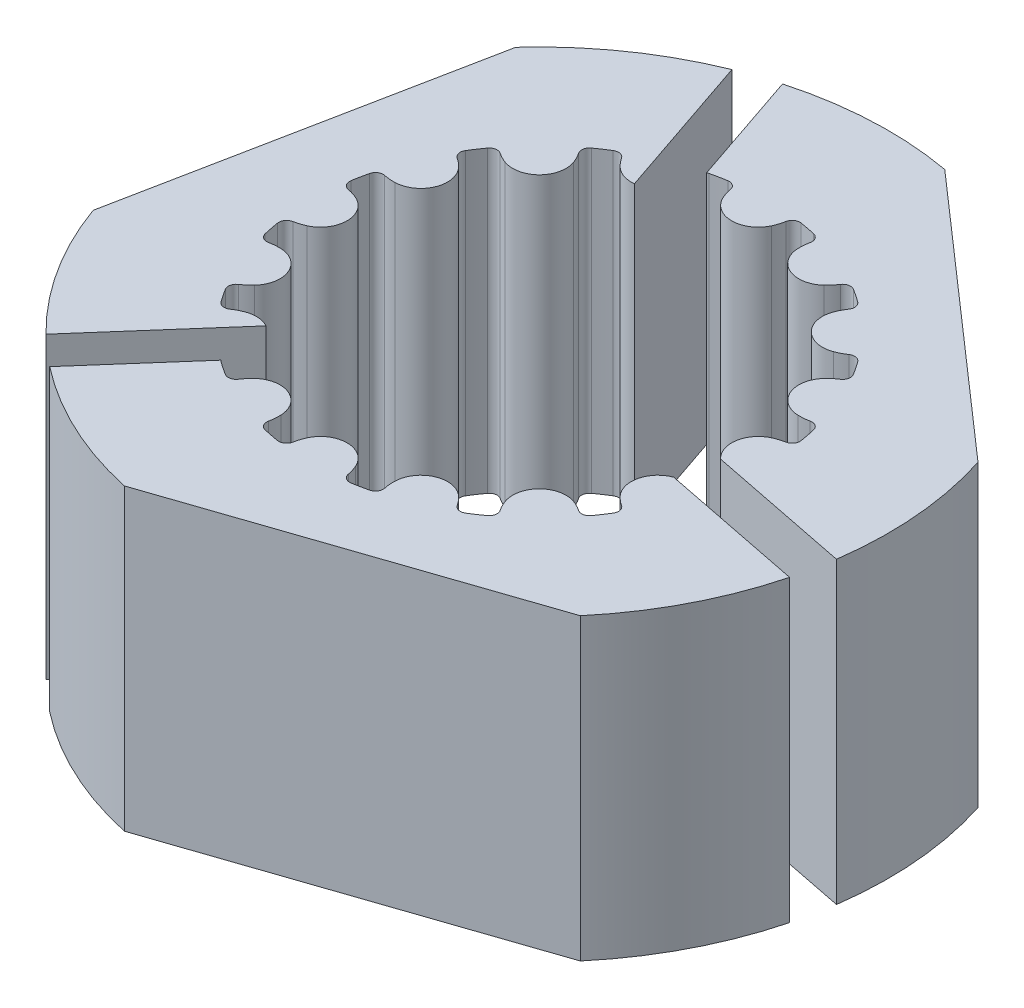
SolidWorks part; units mm, degrees
material "Alum Plate"
ref_plane "Front Plane" through (0, 0, 0) normal (0, 0, 1) x (1, 0, 0)
ref_plane "Top Plane" through (0, 0, 0) normal (0, 1, 0) x (1, 0, 0)
ref_plane "Right Plane" through (0, 0, 0) normal (1, 0, 0) x (0, 0, -1)
other "Bounding Box"
ref_plane "Default Plane" through (-8.9266, -12.7485, 0) normal (-0.1736, 0.9848, 0) x (0.9848, 0.1736, 0)
sketch "Sketch1" plane through (0, 0, 0) normal (0, 1, 0) x (1, 0, 0)
  line L0 (0, -7.8245) -> (0, 0) construction
  circle A0 centre (0, 0) radius 2.5
  arc B0 (-1.8508, -6.777) -> (-1.6633, -7.0715) centre (-1.6061, -6.8282) ccw
  arc B1 (-1.6633, -7.0715) -> (-1.1695, -7.1697) centre (0, 0) ccw
  arc B2 (-1.1695, -7.1697) -> (-0.8836, -6.9694) centre (-1.1292, -6.923) ccw
  arc B3 (-0.7739, -6.6229) -> (-0.8836, -6.9694) centre (0.61, -7.2516) ccw
  arc B4 (0.7739, -6.6229) -> (-0.7739, -6.6229) centre (0, -6.9745) ccw
  arc B5 (0.8836, -6.9694) -> (0.7739, -6.6229) centre (-0.61, -7.2516) ccw
  arc B6 (0.8836, -6.9694) -> (1.1695, -7.1697) centre (1.1292, -6.923) ccw
  arc B7 (1.1695, -7.1697) -> (1.6633, -7.0715) centre (0, 0) ccw
  arc B8 (1.6633, -7.0715) -> (1.8508, -6.777) centre (1.6061, -6.8282) ccw
  arc B9 (1.8195, -6.4149) -> (1.8508, -6.777) centre (3.3386, -6.4662) ccw
  arc B10 (3.2495, -5.8226) -> (1.8195, -6.4149) centre (2.669, -6.4436) ccw
  arc B11 (3.4834, -6.1008) -> (3.2495, -5.8226) centre (2.2115, -6.9331) ccw
  arc B12 (3.4834, -6.1008) -> (3.8242, -6.1764) centre (3.6926, -5.9639) ccw
  arc B13 (3.8242, -6.1764) -> (4.2428, -5.8967) centre (0, 0) ccw
  arc B14 (4.2428, -5.8967) -> (4.3033, -5.5529) centre (4.0968, -5.6938) ccw
  arc B15 (4.1359, -5.2303) -> (4.3033, -5.5529) centre (5.559, -4.6963) ccw
  arc B16 (5.2303, -4.1359) -> (4.1359, -5.2303) centre (4.9317, -4.9317) ccw
  arc B17 (5.5529, -4.3033) -> (5.2303, -4.1359) centre (4.6963, -5.559) ccw
  arc B18 (5.5529, -4.3033) -> (5.8967, -4.2428) centre (5.6938, -4.0968) ccw
  arc B19 (5.8967, -4.2428) -> (6.1764, -3.8242) centre (0, 0) ccw
  arc B20 (6.1764, -3.8242) -> (6.1008, -3.4834) centre (5.9639, -3.6926) ccw
  arc B21 (5.8226, -3.2495) -> (6.1008, -3.4834) centre (6.9331, -2.2115) ccw
  arc B22 (6.4149, -1.8195) -> (5.8226, -3.2495) centre (6.4436, -2.669) ccw
  arc B23 (6.777, -1.8508) -> (6.4149, -1.8195) centre (6.4662, -3.3386) ccw
  arc B24 (6.777, -1.8508) -> (7.0715, -1.6633) centre (6.8282, -1.6061) ccw
  arc B25 (7.0715, -1.6633) -> (7.1697, -1.1695) centre (0, 0) ccw
  arc B26 (7.1697, -1.1695) -> (6.9694, -0.8836) centre (6.923, -1.1292) ccw
  arc B27 (6.6229, -0.7739) -> (6.9694, -0.8836) centre (7.2516, 0.61) ccw
  arc B28 (6.6229, 0.7739) -> (6.6229, -0.7739) centre (6.9745, 0) ccw
  arc B29 (6.9694, 0.8836) -> (6.6229, 0.7739) centre (7.2516, -0.61) ccw
  arc B30 (6.9694, 0.8836) -> (7.1697, 1.1695) centre (6.923, 1.1292) ccw
  arc B31 (7.1697, 1.1695) -> (7.0715, 1.6633) centre (0, 0) ccw
  arc B32 (7.0715, 1.6633) -> (6.777, 1.8508) centre (6.8282, 1.6061) ccw
  arc B33 (6.4149, 1.8195) -> (6.777, 1.8508) centre (6.4662, 3.3386) ccw
  arc B34 (5.8226, 3.2495) -> (6.4149, 1.8195) centre (6.4436, 2.669) ccw
  arc B35 (6.1008, 3.4834) -> (5.8226, 3.2495) centre (6.9331, 2.2115) ccw
  arc B36 (6.1008, 3.4834) -> (6.1764, 3.8242) centre (5.9639, 3.6926) ccw
  arc B37 (6.1764, 3.8242) -> (5.8967, 4.2428) centre (0, 0) ccw
  arc B38 (5.8967, 4.2428) -> (5.5529, 4.3033) centre (5.6938, 4.0968) ccw
  arc B39 (5.2303, 4.1359) -> (5.5529, 4.3033) centre (4.6963, 5.559) ccw
  arc B40 (4.1359, 5.2303) -> (5.2303, 4.1359) centre (4.9317, 4.9317) ccw
  arc B41 (4.3033, 5.5529) -> (4.1359, 5.2303) centre (5.559, 4.6963) ccw
  arc B42 (4.3033, 5.5529) -> (4.2428, 5.8967) centre (4.0968, 5.6938) ccw
  arc B43 (4.2428, 5.8967) -> (3.8242, 6.1764) centre (0, 0) ccw
  arc B44 (3.8242, 6.1764) -> (3.4834, 6.1008) centre (3.6926, 5.9639) ccw
  arc B45 (3.2495, 5.8226) -> (3.4834, 6.1008) centre (2.2115, 6.9331) ccw
  arc B46 (1.8195, 6.4149) -> (3.2495, 5.8226) centre (2.669, 6.4436) ccw
  arc B47 (1.8508, 6.777) -> (1.8195, 6.4149) centre (3.3386, 6.4662) ccw
  arc B48 (1.8508, 6.777) -> (1.6633, 7.0715) centre (1.6061, 6.8282) ccw
  arc B49 (1.6633, 7.0715) -> (1.1695, 7.1697) centre (0, 0) ccw
  arc B50 (1.1695, 7.1697) -> (0.8836, 6.9694) centre (1.1292, 6.923) ccw
  arc B51 (0.7739, 6.6229) -> (0.8836, 6.9694) centre (-0.61, 7.2516) ccw
  arc B52 (-0.7739, 6.6229) -> (0.7739, 6.6229) centre (0, 6.9745) ccw
  arc B53 (-0.8836, 6.9694) -> (-0.7739, 6.6229) centre (0.61, 7.2516) ccw
  arc B54 (-0.8836, 6.9694) -> (-1.1695, 7.1697) centre (-1.1292, 6.923) ccw
  arc B55 (-1.1695, 7.1697) -> (-1.6633, 7.0715) centre (0, 0) ccw
  arc B56 (-1.6633, 7.0715) -> (-1.8508, 6.777) centre (-1.6061, 6.8282) ccw
  arc B57 (-1.8195, 6.4149) -> (-1.8508, 6.777) centre (-3.3386, 6.4662) ccw
  arc B58 (-3.2495, 5.8226) -> (-1.8195, 6.4149) centre (-2.669, 6.4436) ccw
  arc B59 (-3.4834, 6.1008) -> (-3.2495, 5.8226) centre (-2.2115, 6.9331) ccw
  arc B60 (-3.4834, 6.1008) -> (-3.8242, 6.1764) centre (-3.6926, 5.9639) ccw
  arc B61 (-3.8242, 6.1764) -> (-4.2428, 5.8967) centre (0, 0) ccw
  arc B62 (-4.2428, 5.8967) -> (-4.3033, 5.5529) centre (-4.0968, 5.6938) ccw
  arc B63 (-4.1359, 5.2303) -> (-4.3033, 5.5529) centre (-5.559, 4.6963) ccw
  arc B64 (-5.2303, 4.1359) -> (-4.1359, 5.2303) centre (-4.9317, 4.9317) ccw
  arc B65 (-5.5529, 4.3033) -> (-5.2303, 4.1359) centre (-4.6963, 5.559) ccw
  arc B66 (-5.5529, 4.3033) -> (-5.8967, 4.2428) centre (-5.6938, 4.0968) ccw
  arc B67 (-5.8967, 4.2428) -> (-6.1764, 3.8242) centre (0, 0) ccw
  arc B68 (-6.1764, 3.8242) -> (-6.1008, 3.4834) centre (-5.9639, 3.6926) ccw
  arc B69 (-5.8226, 3.2495) -> (-6.1008, 3.4834) centre (-6.9331, 2.2115) ccw
  arc B70 (-6.4149, 1.8195) -> (-5.8226, 3.2495) centre (-6.4436, 2.669) ccw
  arc B71 (-6.777, 1.8508) -> (-6.4149, 1.8195) centre (-6.4662, 3.3386) ccw
  arc B72 (-6.777, 1.8508) -> (-7.0715, 1.6633) centre (-6.8282, 1.6061) ccw
  arc B73 (-7.0715, 1.6633) -> (-7.1697, 1.1695) centre (0, 0) ccw
  arc B74 (-7.1697, 1.1695) -> (-6.9694, 0.8836) centre (-6.923, 1.1292) ccw
  arc B75 (-6.6229, 0.7739) -> (-6.9694, 0.8836) centre (-7.2516, -0.61) ccw
  arc B76 (-6.6229, -0.7739) -> (-6.6229, 0.7739) centre (-6.9745, 0) ccw
  arc B77 (-6.9694, -0.8836) -> (-6.6229, -0.7739) centre (-7.2516, 0.61) ccw
  arc B78 (-6.9694, -0.8836) -> (-7.1697, -1.1695) centre (-6.923, -1.1292) ccw
  arc B79 (-7.1697, -1.1695) -> (-7.0715, -1.6633) centre (0, 0) ccw
  arc B80 (-7.0715, -1.6633) -> (-6.777, -1.8508) centre (-6.8282, -1.6061) ccw
  arc B81 (-6.4149, -1.8195) -> (-6.777, -1.8508) centre (-6.4662, -3.3386) ccw
  arc B82 (-5.8226, -3.2495) -> (-6.4149, -1.8195) centre (-6.4436, -2.669) ccw
  arc B83 (-6.1008, -3.4834) -> (-5.8226, -3.2495) centre (-6.9331, -2.2115) ccw
  arc B84 (-6.1008, -3.4834) -> (-6.1764, -3.8242) centre (-5.9639, -3.6926) ccw
  arc B85 (-6.1764, -3.8242) -> (-5.8967, -4.2428) centre (0, 0) ccw
  arc B86 (-5.8967, -4.2428) -> (-5.5529, -4.3033) centre (-5.6938, -4.0968) ccw
  arc B87 (-5.2303, -4.1359) -> (-5.5529, -4.3033) centre (-4.6963, -5.559) ccw
  arc B88 (-4.1359, -5.2303) -> (-5.2303, -4.1359) centre (-4.9317, -4.9317) ccw
  arc B89 (-4.3033, -5.5529) -> (-4.1359, -5.2303) centre (-5.559, -4.6963) ccw
  arc B90 (-4.3033, -5.5529) -> (-4.2428, -5.8967) centre (-4.0968, -5.6938) ccw
  arc B91 (-4.2428, -5.8967) -> (-3.8242, -6.1764) centre (0, 0) ccw
  arc B92 (-3.8242, -6.1764) -> (-3.4834, -6.1008) centre (-3.6926, -5.9639) ccw
  arc B93 (-3.2495, -5.8226) -> (-3.4834, -6.1008) centre (-2.2115, -6.9331) ccw
  arc B94 (-1.8195, -6.4149) -> (-3.2495, -5.8226) centre (-2.669, -6.4436) ccw
  arc B95 (-1.8508, -6.777) -> (-1.8195, -6.4149) centre (-3.3386, -6.4662) ccw
  dimension "D1" = 5
sketch_block_instance "Block-GT2 16 Tooth Profile-1"
sketch_block "Block-GT2 16 Tooth Profile"
extrude "Boss-Extrude1" add sketch "Sketch1" along normal mid plane 9.525
sketch "Sketch2" plane through (0, -4.7625, 0) normal (0, -1, 0) x (1, 0, 0)
  circle A0 centre (0, 0) radius 7.9375
  circle A1 centre (0, 0) radius 2.5 construction
  circle A2 centre (0, 0) radius 2.5
  dimension "D1" = 15.875
extrude "Boss-Extrude2" add sketch "Sketch2" along normal blind 0.762 separate body
sketch "Sketch4" plane through (0, -4.7625, 0) normal (0, -1, 0) x (1, 0, 0)
  line L0 (-4.3596, 0.8672) -> (0, 0) construction
  line L1 (0, 0) -> (4.3596, -0.8672) construction
  line L2 (-7.1249, 1.4172) -> (-4.3596, 0.8672) construction
  circle A0 centre (-4.3596, 0.8672) radius 1
  circle A1 centre (4.3596, -0.8672) radius 1
  arc A2 (-7.0715, 1.6633) -> (-7.1697, 1.1695) centre (0, 0) ccw construction
  dimension "D1" = 2
  dimension "D2" = 4.445
extrude "Cut-Extrude2" cut sketch "Sketch4" against normal through all
sketch "Sketch5" plane through (0, -4.7625, 0) normal (0, 1, 0) x (1, 0, 0)
  circle A0 centre (-4.3596, -0.8672) radius 1.25
  circle A1 centre (4.3596, 0.8672) radius 1.25
  dimension "D1" = 2.5
extrude "Cut-Extrude3" cut sketch "Sketch5" against normal through all
delete or keep bodies "Body-Delete/Keep 1" [suppressed] type delete bodies bodies 111
delete or keep bodies "Body-Delete/Keep 2" [suppressed] type delete bodies bodies 108
sketch "Sketch6" plane through (0, 4.7625, 0) normal (0, 1, 0) x (1, 0, 0)
  line L2 (0, 0) -> (-3.572, 10.5228) construction
  line L3 (-7.327, -8.3548) -> (0, 0) construction
  line L4 (0, 0) -> (10.899, -2.1679) construction
  line L5 (-3.572, 10.5228) -> (10.899, -2.1679) construction
  line L6 (10.899, -2.1679) -> (-7.327, -8.3548) construction
  line L7 (-7.327, -8.3548) -> (-3.572, 10.5228) construction
  line L8 (-3.572, 10.5228) -> (-10.899, 2.1679) construction
  line L9 (-10.899, 2.1679) -> (-7.327, -8.3548) construction
  line L10 (-7.327, -8.3548) -> (3.572, -10.5228) construction
  line L11 (3.572, -10.5228) -> (10.899, -2.1679) construction
  line L12 (10.899, -2.1679) -> (7.327, 8.3548) construction
  line L13 (7.327, 8.3548) -> (-3.572, 10.5228) construction
  line L14 (0.6013, 0.2041) -> (-2.9707, 10.7269)
  line L15 (-6.8496, -8.7735) -> (0.4774, -0.4187)
  line L16 (-0.1239, -0.6228) -> (10.7751, -2.7907)
  line L17 (-0.6013, -0.2041) -> (-4.1733, 10.3186)
  line L18 (-7.8044, -7.9361) -> (-0.4774, 0.4187)
  line L19 (0.1239, 0.6228) -> (11.0229, -1.5451)
  line L20 (-8.2253, 7.4721) -> (-10.4586, -3.7556)
  line L21 (-2.3583, -10.8594) -> (8.4818, -7.1797)
  line L22 (1.9769, 10.9352) -> (10.5837, 3.3873)
  line L23 (7.327, 8.3548) -> (6.2803, 7.1613) construction
  line L24 (3.0617, -9.0195) -> (3.572, -10.5228) construction
  line L25 (-10.899, 2.1679) -> (-9.342, 1.8582) construction
  circle A1 centre (0, 0) radius 11.1125
  arc A96 (-1.8508, -6.777) -> (-1.8195, -6.4149) centre (-3.3386, -6.4662) ccw
  arc A97 (-1.8508, -6.777) -> (-1.6633, -7.0715) centre (-1.6061, -6.8282) ccw
  arc A98 (-1.6633, -7.0715) -> (-1.1695, -7.1697) centre (0, 0) ccw
  arc A99 (-1.1695, -7.1697) -> (-0.8836, -6.9694) centre (-1.1292, -6.923) ccw
  arc A100 (-0.7739, -6.6229) -> (-0.8836, -6.9694) centre (0.61, -7.2516) ccw
  arc A101 (0.7739, -6.6229) -> (-0.7739, -6.6229) centre (0, -6.9745) ccw
  arc A102 (0.8836, -6.9694) -> (0.7739, -6.6229) centre (-0.61, -7.2516) ccw
  arc A103 (0.8836, -6.9694) -> (1.1695, -7.1697) centre (1.1292, -6.923) ccw
  arc A104 (1.1695, -7.1697) -> (1.6633, -7.0715) centre (0, 0) ccw
  arc A105 (1.6633, -7.0715) -> (1.8508, -6.777) centre (1.6061, -6.8282) ccw
  arc A106 (1.8195, -6.4149) -> (1.8508, -6.777) centre (3.3386, -6.4662) ccw
  arc A107 (3.2495, -5.8226) -> (1.8195, -6.4149) centre (2.669, -6.4436) ccw
  arc A108 (3.4834, -6.1008) -> (3.2495, -5.8226) centre (2.2115, -6.9331) ccw
  arc A109 (3.4834, -6.1008) -> (3.8242, -6.1764) centre (3.6926, -5.9639) ccw
  arc A110 (3.8242, -6.1764) -> (4.2428, -5.8967) centre (0, 0) ccw
  arc A111 (4.2428, -5.8967) -> (4.3033, -5.5529) centre (4.0968, -5.6938) ccw
  arc A112 (4.1359, -5.2303) -> (4.3033, -5.5529) centre (5.559, -4.6963) ccw
  arc A113 (5.2303, -4.1359) -> (4.1359, -5.2303) centre (4.9317, -4.9317) ccw
  arc A114 (5.5529, -4.3033) -> (5.2303, -4.1359) centre (4.6963, -5.559) ccw
  arc A115 (5.5529, -4.3033) -> (5.8967, -4.2428) centre (5.6938, -4.0968) ccw
  arc A116 (5.8967, -4.2428) -> (6.1764, -3.8242) centre (0, 0) ccw
  arc A117 (6.1764, -3.8242) -> (6.1008, -3.4834) centre (5.9639, -3.6926) ccw
  arc A118 (5.8226, -3.2495) -> (6.1008, -3.4834) centre (6.9331, -2.2115) ccw
  arc A119 (6.4149, -1.8195) -> (5.8226, -3.2495) centre (6.4436, -2.669) ccw
  arc A120 (6.777, -1.8508) -> (6.4149, -1.8195) centre (6.4662, -3.3386) ccw
  arc A121 (6.777, -1.8508) -> (7.0715, -1.6633) centre (6.8282, -1.6061) ccw
  arc A122 (7.0715, -1.6633) -> (7.1697, -1.1695) centre (0, 0) ccw
  arc A123 (7.1697, -1.1695) -> (6.9694, -0.8836) centre (6.923, -1.1292) ccw
  arc A124 (6.6229, -0.7739) -> (6.9694, -0.8836) centre (7.2516, 0.61) ccw
  arc A125 (6.6229, 0.7739) -> (6.6229, -0.7739) centre (6.9745, 0) ccw
  arc A126 (6.9694, 0.8836) -> (6.6229, 0.7739) centre (7.2516, -0.61) ccw
  arc A127 (6.9694, 0.8836) -> (7.1697, 1.1695) centre (6.923, 1.1292) ccw
  arc A128 (7.1697, 1.1695) -> (7.0715, 1.6633) centre (0, 0) ccw
  arc A129 (7.0715, 1.6633) -> (6.777, 1.8508) centre (6.8282, 1.6061) ccw
  arc A130 (6.4149, 1.8195) -> (6.777, 1.8508) centre (6.4662, 3.3386) ccw
  arc A131 (5.8226, 3.2495) -> (6.4149, 1.8195) centre (6.4436, 2.669) ccw
  arc A132 (6.1008, 3.4834) -> (5.8226, 3.2495) centre (6.9331, 2.2115) ccw
  arc A133 (6.1008, 3.4834) -> (6.1764, 3.8242) centre (5.9639, 3.6926) ccw
  arc A134 (6.1764, 3.8242) -> (5.8967, 4.2428) centre (0, 0) ccw
  arc A135 (5.8967, 4.2428) -> (5.5529, 4.3033) centre (5.6938, 4.0968) ccw
  arc A136 (5.2303, 4.1359) -> (5.5529, 4.3033) centre (4.6963, 5.559) ccw
  arc A137 (4.1359, 5.2303) -> (5.2303, 4.1359) centre (4.9317, 4.9317) ccw
  arc A138 (4.3033, 5.5529) -> (4.1359, 5.2303) centre (5.559, 4.6963) ccw
  arc A139 (4.3033, 5.5529) -> (4.2428, 5.8967) centre (4.0968, 5.6938) ccw
  arc A140 (4.2428, 5.8967) -> (3.8242, 6.1764) centre (0, 0) ccw
  arc A141 (3.8242, 6.1764) -> (3.4834, 6.1008) centre (3.6926, 5.9639) ccw
  arc A142 (3.2495, 5.8226) -> (3.4834, 6.1008) centre (2.2115, 6.9331) ccw
  arc A143 (1.8195, 6.4149) -> (3.2495, 5.8226) centre (2.669, 6.4436) ccw
  arc A144 (1.8508, 6.777) -> (1.8195, 6.4149) centre (3.3386, 6.4662) ccw
  arc A145 (1.8508, 6.777) -> (1.6633, 7.0715) centre (1.6061, 6.8282) ccw
  arc A146 (1.6633, 7.0715) -> (1.1695, 7.1697) centre (0, 0) ccw
  arc A147 (1.1695, 7.1697) -> (0.8836, 6.9694) centre (1.1292, 6.923) ccw
  arc A148 (0.7739, 6.6229) -> (0.8836, 6.9694) centre (-0.61, 7.2516) ccw
  arc A149 (-0.7739, 6.6229) -> (0.7739, 6.6229) centre (0, 6.9745) ccw
  arc A150 (-0.8836, 6.9694) -> (-0.7739, 6.6229) centre (0.61, 7.2516) ccw
  arc A151 (-0.8836, 6.9694) -> (-1.1695, 7.1697) centre (-1.1292, 6.923) ccw
  arc A152 (-1.1695, 7.1697) -> (-1.6633, 7.0715) centre (0, 0) ccw
  arc A153 (-1.6633, 7.0715) -> (-1.8508, 6.777) centre (-1.6061, 6.8282) ccw
  arc A154 (-1.8195, 6.4149) -> (-1.8508, 6.777) centre (-3.3386, 6.4662) ccw
  arc A155 (-3.2495, 5.8226) -> (-1.8195, 6.4149) centre (-2.669, 6.4436) ccw
  arc A156 (-3.4834, 6.1008) -> (-3.2495, 5.8226) centre (-2.2115, 6.9331) ccw
  arc A157 (-3.4834, 6.1008) -> (-3.8242, 6.1764) centre (-3.6926, 5.9639) ccw
  arc A158 (-3.8242, 6.1764) -> (-4.2428, 5.8967) centre (0, 0) ccw
  arc A159 (-4.2428, 5.8967) -> (-4.3033, 5.5529) centre (-4.0968, 5.6938) ccw
  arc A160 (-4.1359, 5.2303) -> (-4.3033, 5.5529) centre (-5.559, 4.6963) ccw
  arc A161 (-5.2303, 4.1359) -> (-4.1359, 5.2303) centre (-4.9317, 4.9317) ccw
  arc A162 (-5.5529, 4.3033) -> (-5.2303, 4.1359) centre (-4.6963, 5.559) ccw
  arc A163 (-5.5529, 4.3033) -> (-5.8967, 4.2428) centre (-5.6938, 4.0968) ccw
  arc A164 (-5.8967, 4.2428) -> (-6.1764, 3.8242) centre (0, 0) ccw
  arc A165 (-6.1764, 3.8242) -> (-6.1008, 3.4834) centre (-5.9639, 3.6926) ccw
  arc A166 (-5.8226, 3.2495) -> (-6.1008, 3.4834) centre (-6.9331, 2.2115) ccw
  arc A167 (-6.4149, 1.8195) -> (-5.8226, 3.2495) centre (-6.4436, 2.669) ccw
  arc A168 (-6.777, 1.8508) -> (-6.4149, 1.8195) centre (-6.4662, 3.3386) ccw
  arc A169 (-6.777, 1.8508) -> (-7.0715, 1.6633) centre (-6.8282, 1.6061) ccw
  arc A170 (-7.0715, 1.6633) -> (-7.1697, 1.1695) centre (0, 0) ccw
  arc A171 (-7.1697, 1.1695) -> (-6.9694, 0.8836) centre (-6.923, 1.1292) ccw
  arc A172 (-6.6229, 0.7739) -> (-6.9694, 0.8836) centre (-7.2516, -0.61) ccw
  arc A173 (-6.6229, -0.7739) -> (-6.6229, 0.7739) centre (-6.9745, 0) ccw
  arc A174 (-6.9694, -0.8836) -> (-6.6229, -0.7739) centre (-7.2516, 0.61) ccw
  arc A175 (-6.9694, -0.8836) -> (-7.1697, -1.1695) centre (-6.923, -1.1292) ccw
  arc A176 (-7.1697, -1.1695) -> (-7.0715, -1.6633) centre (0, 0) ccw
  arc A177 (-7.0715, -1.6633) -> (-6.777, -1.8508) centre (-6.8282, -1.6061) ccw
  arc A178 (-6.4149, -1.8195) -> (-6.777, -1.8508) centre (-6.4662, -3.3386) ccw
  arc A179 (-5.8226, -3.2495) -> (-6.4149, -1.8195) centre (-6.4436, -2.669) ccw
  arc A180 (-6.1008, -3.4834) -> (-5.8226, -3.2495) centre (-6.9331, -2.2115) ccw
  arc A181 (-6.1008, -3.4834) -> (-6.1764, -3.8242) centre (-5.9639, -3.6926) ccw
  arc A182 (-6.1764, -3.8242) -> (-5.8967, -4.2428) centre (0, 0) ccw
  arc A183 (-5.8967, -4.2428) -> (-5.5529, -4.3033) centre (-5.6938, -4.0968) ccw
  arc A184 (-5.2303, -4.1359) -> (-5.5529, -4.3033) centre (-4.6963, -5.559) ccw
  arc A185 (-4.1359, -5.2303) -> (-5.2303, -4.1359) centre (-4.9317, -4.9317) ccw
  arc A186 (-4.3033, -5.5529) -> (-4.1359, -5.2303) centre (-5.559, -4.6963) ccw
  arc A187 (-4.3033, -5.5529) -> (-4.2428, -5.8967) centre (-4.0968, -5.6938) ccw
  arc A188 (-4.2428, -5.8967) -> (-3.8242, -6.1764) centre (0, 0) ccw
  arc A189 (-3.8242, -6.1764) -> (-3.4834, -6.1008) centre (-3.6926, -5.9639) ccw
  arc A190 (-3.2495, -5.8226) -> (-3.4834, -6.1008) centre (-2.2115, -6.9331) ccw
  arc A191 (-1.8195, -6.4149) -> (-3.2495, -5.8226) centre (-2.669, -6.4436) ccw
  arc A192 (-1.8508, -6.777) -> (-1.8195, -6.4149) centre (-3.3386, -6.4662) ccw
  arc A193 (-1.8508, -6.777) -> (-1.6633, -7.0715) centre (-1.6061, -6.8282) ccw
  arc A194 (-1.6633, -7.0715) -> (-1.1695, -7.1697) centre (0, 0) ccw
  arc A195 (-1.1695, -7.1697) -> (-0.8836, -6.9694) centre (-1.1292, -6.923) ccw
  arc A196 (-0.7739, -6.6229) -> (-0.8836, -6.9694) centre (0.61, -7.2516) ccw
  arc A197 (0.7739, -6.6229) -> (-0.7739, -6.6229) centre (0, -6.9745) ccw
  arc A198 (0.8836, -6.9694) -> (0.7739, -6.6229) centre (-0.61, -7.2516) ccw
  arc A199 (0.8836, -6.9694) -> (1.1695, -7.1697) centre (1.1292, -6.923) ccw
  arc A200 (1.1695, -7.1697) -> (1.6633, -7.0715) centre (0, 0) ccw
  arc A201 (1.6633, -7.0715) -> (1.8508, -6.777) centre (1.6061, -6.8282) ccw
  arc A202 (1.8195, -6.4149) -> (1.8508, -6.777) centre (3.3386, -6.4662) ccw
  arc A203 (3.2495, -5.8226) -> (1.8195, -6.4149) centre (2.669, -6.4436) ccw
  arc A204 (3.4834, -6.1008) -> (3.2495, -5.8226) centre (2.2115, -6.9331) ccw
  arc A205 (3.4834, -6.1008) -> (3.8242, -6.1764) centre (3.6926, -5.9639) ccw
  arc A206 (3.8242, -6.1764) -> (4.2428, -5.8967) centre (0, 0) ccw
  arc A207 (4.2428, -5.8967) -> (4.3033, -5.5529) centre (4.0968, -5.6938) ccw
  arc A208 (4.1359, -5.2303) -> (4.3033, -5.5529) centre (5.559, -4.6963) ccw
  arc A209 (5.2303, -4.1359) -> (4.1359, -5.2303) centre (4.9317, -4.9317) ccw
  arc A210 (5.5529, -4.3033) -> (5.2303, -4.1359) centre (4.6963, -5.559) ccw
  arc A211 (5.5529, -4.3033) -> (5.8967, -4.2428) centre (5.6938, -4.0968) ccw
  arc A212 (5.8967, -4.2428) -> (6.1764, -3.8242) centre (0, 0) ccw
  arc A213 (6.1764, -3.8242) -> (6.1008, -3.4834) centre (5.9639, -3.6926) ccw
  arc A214 (5.8226, -3.2495) -> (6.1008, -3.4834) centre (6.9331, -2.2115) ccw
  arc A215 (6.4149, -1.8195) -> (5.8226, -3.2495) centre (6.4436, -2.669) ccw
  arc A216 (6.777, -1.8508) -> (6.4149, -1.8195) centre (6.4662, -3.3386) ccw
  arc A217 (6.777, -1.8508) -> (7.0715, -1.6633) centre (6.8282, -1.6061) ccw
  arc A218 (7.0715, -1.6633) -> (7.1697, -1.1695) centre (0, 0) ccw
  arc A219 (7.1697, -1.1695) -> (6.9694, -0.8836) centre (6.923, -1.1292) ccw
  arc A220 (6.6229, -0.7739) -> (6.9694, -0.8836) centre (7.2516, 0.61) ccw
  arc A221 (6.6229, 0.7739) -> (6.6229, -0.7739) centre (6.9745, 0) ccw
  arc A222 (6.9694, 0.8836) -> (6.6229, 0.7739) centre (7.2516, -0.61) ccw
  arc A223 (6.9694, 0.8836) -> (7.1697, 1.1695) centre (6.923, 1.1292) ccw
  arc A224 (7.1697, 1.1695) -> (7.0715, 1.6633) centre (0, 0) ccw
  arc A225 (7.0715, 1.6633) -> (6.777, 1.8508) centre (6.8282, 1.6061) ccw
  arc A226 (6.4149, 1.8195) -> (6.777, 1.8508) centre (6.4662, 3.3386) ccw
  arc A227 (5.8226, 3.2495) -> (6.4149, 1.8195) centre (6.4436, 2.669) ccw
  arc A228 (6.1008, 3.4834) -> (5.8226, 3.2495) centre (6.9331, 2.2115) ccw
  arc A229 (6.1008, 3.4834) -> (6.1764, 3.8242) centre (5.9639, 3.6926) ccw
  arc A230 (6.1764, 3.8242) -> (5.8967, 4.2428) centre (0, 0) ccw
  arc A231 (5.8967, 4.2428) -> (5.5529, 4.3033) centre (5.6938, 4.0968) ccw
  arc A232 (5.2303, 4.1359) -> (5.5529, 4.3033) centre (4.6963, 5.559) ccw
  arc A233 (4.1359, 5.2303) -> (5.2303, 4.1359) centre (4.9317, 4.9317) ccw
  arc A234 (4.3033, 5.5529) -> (4.1359, 5.2303) centre (5.559, 4.6963) ccw
  arc A235 (4.3033, 5.5529) -> (4.2428, 5.8967) centre (4.0968, 5.6938) ccw
  arc A236 (4.2428, 5.8967) -> (3.8242, 6.1764) centre (0, 0) ccw
  arc A237 (3.8242, 6.1764) -> (3.4834, 6.1008) centre (3.6926, 5.9639) ccw
  arc A238 (3.2495, 5.8226) -> (3.4834, 6.1008) centre (2.2115, 6.9331) ccw
  arc A239 (1.8195, 6.4149) -> (3.2495, 5.8226) centre (2.669, 6.4436) ccw
  arc A240 (1.8508, 6.777) -> (1.8195, 6.4149) centre (3.3386, 6.4662) ccw
  arc A241 (1.8508, 6.777) -> (1.6633, 7.0715) centre (1.6061, 6.8282) ccw
  arc A242 (1.6633, 7.0715) -> (1.1695, 7.1697) centre (0, 0) ccw
  arc A243 (1.1695, 7.1697) -> (0.8836, 6.9694) centre (1.1292, 6.923) ccw
  arc A244 (0.7739, 6.6229) -> (0.8836, 6.9694) centre (-0.61, 7.2516) ccw
  arc A245 (-0.7739, 6.6229) -> (0.7739, 6.6229) centre (0, 6.9745) ccw
  arc A246 (-0.8836, 6.9694) -> (-0.7739, 6.6229) centre (0.61, 7.2516) ccw
  arc A247 (-0.8836, 6.9694) -> (-1.1695, 7.1697) centre (-1.1292, 6.923) ccw
  arc A248 (-1.1695, 7.1697) -> (-1.6633, 7.0715) centre (0, 0) ccw
  arc A249 (-1.6633, 7.0715) -> (-1.8508, 6.777) centre (-1.6061, 6.8282) ccw
  arc A250 (-1.8195, 6.4149) -> (-1.8508, 6.777) centre (-3.3386, 6.4662) ccw
  arc A251 (-3.2495, 5.8226) -> (-1.8195, 6.4149) centre (-2.669, 6.4436) ccw
  arc A252 (-3.4834, 6.1008) -> (-3.2495, 5.8226) centre (-2.2115, 6.9331) ccw
  arc A253 (-3.4834, 6.1008) -> (-3.8242, 6.1764) centre (-3.6926, 5.9639) ccw
  arc A254 (-3.8242, 6.1764) -> (-4.2428, 5.8967) centre (0, 0) ccw
  arc A255 (-4.2428, 5.8967) -> (-4.3033, 5.5529) centre (-4.0968, 5.6938) ccw
  arc A256 (-4.1359, 5.2303) -> (-4.3033, 5.5529) centre (-5.559, 4.6963) ccw
  arc A257 (-5.2303, 4.1359) -> (-4.1359, 5.2303) centre (-4.9317, 4.9317) ccw
  arc A258 (-5.5529, 4.3033) -> (-5.2303, 4.1359) centre (-4.6963, 5.559) ccw
  arc A259 (-5.5529, 4.3033) -> (-5.8967, 4.2428) centre (-5.6938, 4.0968) ccw
  arc A260 (-5.8967, 4.2428) -> (-6.1764, 3.8242) centre (0, 0) ccw
  arc A261 (-6.1764, 3.8242) -> (-6.1008, 3.4834) centre (-5.9639, 3.6926) ccw
  arc A262 (-5.8226, 3.2495) -> (-6.1008, 3.4834) centre (-6.9331, 2.2115) ccw
  arc A263 (-6.4149, 1.8195) -> (-5.8226, 3.2495) centre (-6.4436, 2.669) ccw
  arc A264 (-6.777, 1.8508) -> (-6.4149, 1.8195) centre (-6.4662, 3.3386) ccw
  arc A265 (-6.777, 1.8508) -> (-7.0715, 1.6633) centre (-6.8282, 1.6061) ccw
  arc A266 (-7.0715, 1.6633) -> (-7.1697, 1.1695) centre (0, 0) ccw
  arc A267 (-7.1697, 1.1695) -> (-6.9694, 0.8836) centre (-6.923, 1.1292) ccw
  arc A268 (-6.6229, 0.7739) -> (-6.9694, 0.8836) centre (-7.2516, -0.61) ccw
  arc A269 (-6.6229, -0.7739) -> (-6.6229, 0.7739) centre (-6.9745, 0) ccw
  arc A270 (-6.9694, -0.8836) -> (-6.6229, -0.7739) centre (-7.2516, 0.61) ccw
  arc A271 (-6.9694, -0.8836) -> (-7.1697, -1.1695) centre (-6.923, -1.1292) ccw
  arc A272 (-7.1697, -1.1695) -> (-7.0715, -1.6633) centre (0, 0) ccw
  arc A273 (-7.0715, -1.6633) -> (-6.777, -1.8508) centre (-6.8282, -1.6061) ccw
  arc A274 (-6.4149, -1.8195) -> (-6.777, -1.8508) centre (-6.4662, -3.3386) ccw
  arc A275 (-5.8226, -3.2495) -> (-6.4149, -1.8195) centre (-6.4436, -2.669) ccw
  arc A276 (-6.1008, -3.4834) -> (-5.8226, -3.2495) centre (-6.9331, -2.2115) ccw
  arc A277 (-6.1008, -3.4834) -> (-6.1764, -3.8242) centre (-5.9639, -3.6926) ccw
  arc A278 (-6.1764, -3.8242) -> (-5.8967, -4.2428) centre (0, 0) ccw
  arc A279 (-5.8967, -4.2428) -> (-5.5529, -4.3033) centre (-5.6938, -4.0968) ccw
  arc A280 (-5.2303, -4.1359) -> (-5.5529, -4.3033) centre (-4.6963, -5.559) ccw
  arc A281 (-4.1359, -5.2303) -> (-5.2303, -4.1359) centre (-4.9317, -4.9317) ccw
  arc A282 (-4.3033, -5.5529) -> (-4.1359, -5.2303) centre (-5.559, -4.6963) ccw
  arc A283 (-4.3033, -5.5529) -> (-4.2428, -5.8967) centre (-4.0968, -5.6938) ccw
  arc A284 (-4.2428, -5.8967) -> (-3.8242, -6.1764) centre (0, 0) ccw
  arc A285 (-3.8242, -6.1764) -> (-3.4834, -6.1008) centre (-3.6926, -5.9639) ccw
  arc A286 (-3.2495, -5.8226) -> (-3.4834, -6.1008) centre (-2.2115, -6.9331) ccw
  arc A287 (-1.8195, -6.4149) -> (-3.2495, -5.8226) centre (-2.669, -6.4436) ccw
  point P87 (9.0252, 6.4662)
  point P93 (10.0817, -4.6963)
  point P96 (10.9456, -2.669)
  point P99 (7.1249, -1.4172)
  dimension "D2" = 0.635
  dimension "D4" = 0.635
  dimension "D3" = 22.225
  dimension "D5" = 9.525
  dimension "D1" = 0
extrude "Boss-Extrude3" add sketch "Sketch6" against normal up to surface (9.525 mm away) separate body contours A192 A287 L17 A1 L20 L18 A221 A220 A219 A218 A217 A216 A215 A214 A213 A212 A211 A210 A209 A208 A207 A206 A205 A204 A203 A202 A201 A200 A199 A198 A197 A196 A195 A194 A193 | A284 A283 A282 A281 A280 A279 A278 A277 A276 A275 A274 A273 A272 A271 A270 A269 A268 A267 A266 A265 A264 A263 A262 A261 A260 A259 A258 A257 A256 A255 A254 L19 A1 L22 L14 | L16 A251 A250 A249 A248 A247 A246 A245 A244 A243 A242 A241 A240 A239 A238 A237 A236 A235 A234 A233 A232 A231 A230 A229 A228 A227 A226 A225 A224 A223 A222 A221 L15 A1 L21 region at (4.7876, 4.7625, -5.4005) region at (-3.5574, 4.7625, -7.8865) region at (2.3565, 4.7625, 6.8216) up to face at (-4.3596, -4.7625, 2.1172)
delete or keep bodies "Body-Delete/Keep 3" type delete bodies bodies 108 111
